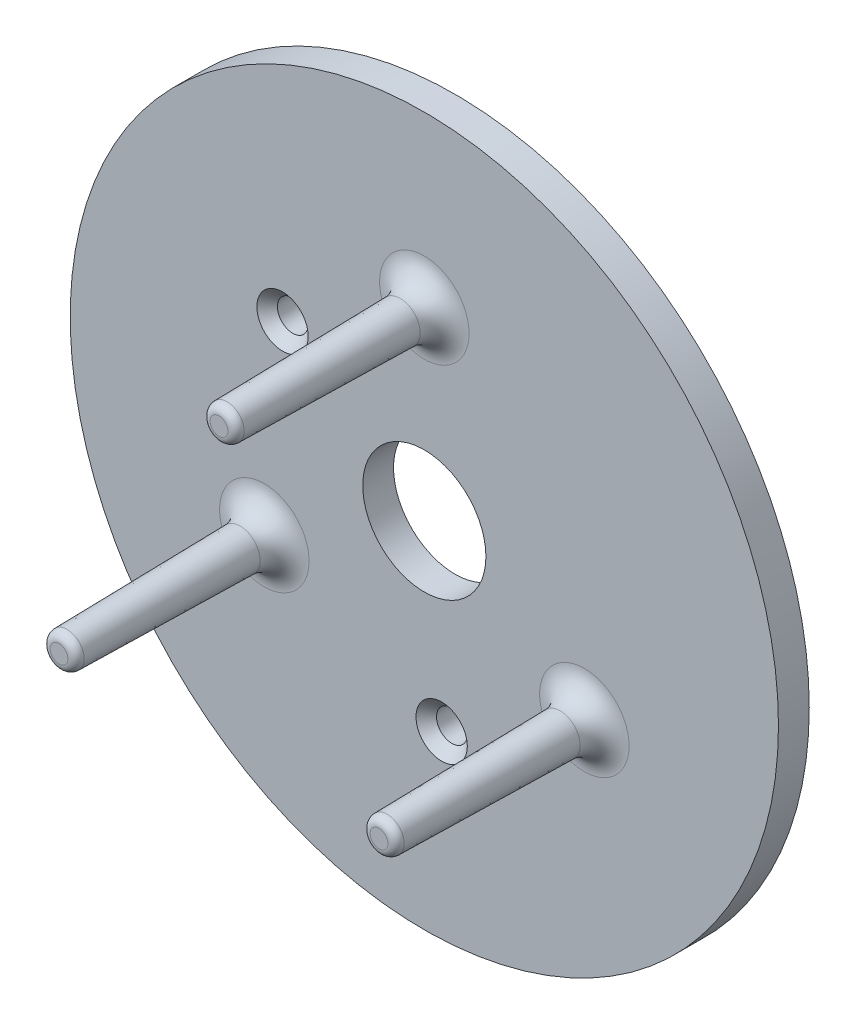
SolidWorks part; units mm, degrees
ref_plane "Front Plane" through (0, 0, 0) normal (1, 0, 0) x (0, 1, 0)
ref_plane "Top Plane" through (0, 0, 0) normal (0, 0, 1) x (0, 1, 0)
ref_plane "Right Plane" through (0, 0, 0) normal (0, 1, 0) x (-1, 0, 0)
sketch "Sketch3" plane through (0, 0, 0) normal (0, 0, 1) x (0, 1, 0)
  circle A0 centre (0, 0) radius 6
  circle A1 centre (0, 0) radius 18 construction
  circle A2 centre (0, 0) radius 34.5
  circle A3 centre (18, 0) radius 2
  dimension "D1" = 69
  dimension "D2" = 12
  dimension "D3" = 36
  dimension "D4" = 4
extrude "Boss-Extrude1" add sketch "Sketch3" along normal blind 3 contours A3 | A2 A3 A0 region at (0, -33.5242, 0) region at (0, 18, 0)
extrude "Boss-Extrude2" add sketch "Sketch3<3>" along normal blind 20 draft 1 from surface contours A3 region at (0, 18, 0) starting at face at (6, 0, 3)
sketch "Sketch3<3>" plane through (0, 0, 0) normal (0, 0, 1) x (0, 1, 0) same geometry as "Sketch3"
fillet "Fillet2" radius 0.8 1 edges at (1.6509, 18, 23)
fillet "Fillet3" radius 2.4 1 edges at (2, 18, 3)
pattern_circular "CirPattern1" count 3 over 360 about axis through (0, 0, 3) along (0, 0, -1) of "Boss-Extrude2", "Fillet2", "Fillet3"
sketch "Sketch4" plane through (0, 0, 3) normal (0, 0, 1) x (1, 0, 0)
  line L0 (-6.0622, -3.5) -> (7.3612, 4.25) construction
  line L1 (1.6878, -16.9234) -> (-13.8122, 9.9234) construction
  circle A0 centre (-6.0622, -3.5) radius 15.5 construction
  circle A1 centre (1.6878, -16.9234) radius 1.5
  circle A3 centre (-13.8122, 9.9234) radius 1.5
  dimension "D1" = 31
  dimension "D2" = 3
  dimension "D3" = 7
extrude "Cut-Extrude1" cut sketch "Sketch4" against normal up to next
chamfer "Chamfer1" distance 1 angle 45 2 edges at (3.1878, -16.9234, 3) (-15.3122, 9.9234, 3)
equation "\"SunTeeth\"= 13"
equation "\"PlanetTeeth\"= 23"
equation "\"module\"= 1"
equation "\"OrbitDiameter\"= \"SunTeeth\" * \"module\" + \"PlanetTeeth\" * \"module\""
equation "\"RingDiameter\"= ( \"SunTeeth\" + 2 * \"PlanetTeeth\" ) * \"module\""
equation "\"SunBore\"= 12"
equation "\"D1@Sketch3\"=\"RingDiameter\"+10mm"
equation "\"D2@Sketch3\"=\"SunBore\""
equation "\"D3@Sketch3\"=\"OrbitDiameter\""
equation "\"BearingBore\"= 4mm"
equation "\"D4@Sketch3\"=\"BearingBore\""
equation "\"ScrewCircle\"=31"
equation "\"D1@Sketch4\"=\"ScrewCircle\""
equation "\"D1@Boss-Extrude2\"=10.00mm*2"
equation "\"D3@Sketch4\"=7"
